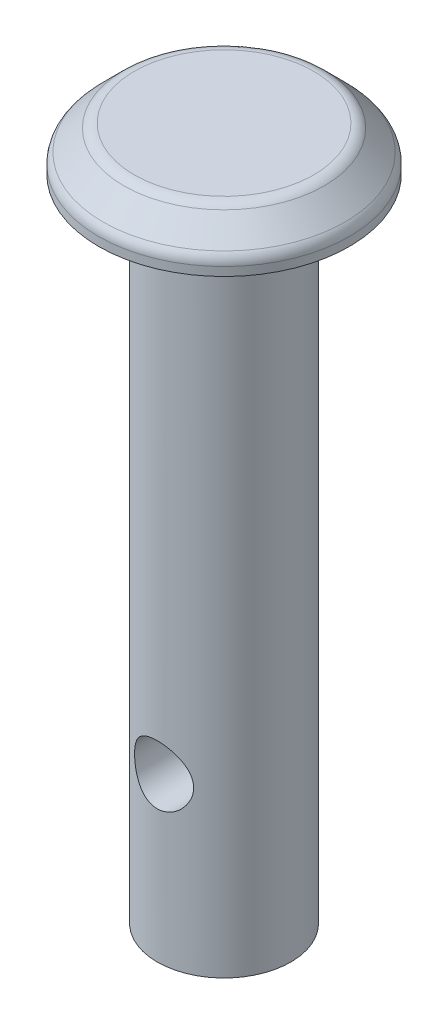
SolidWorks part; units mm, degrees
ref_plane "Front Plane" through (0, 0, 0) normal (0, 0, 1) x (1, 0, 0)
ref_plane "Top Plane" through (0, 0, 0) normal (0, 1, 0) x (1, 0, 0)
ref_plane "Right Plane" through (0, 0, 0) normal (1, 0, 0) x (0, 0, -1)
sketch "Sketch1" plane through (0, 0, 0) normal (0, 1, 0) x (1, 0, 0)
  circle A0 centre (0, 0) radius 2.265
  dimension "D1" = 4.53
extrude "Boss-Extrude1" add sketch "Sketch1" along normal blind 22
sketch "Sketch2" plane through (0, 22, 0) normal (0, 1, 0) x (1, 0, 0)
  circle A0 centre (0, 0) radius 4.25
  dimension "D1" = 8.5
extrude "Boss-Extrude2" add sketch "Sketch2" along normal blind 1.5
chamfer "Chamfer1" distance 1 angle 45 1 edges at (0, 23.5, 4.25)
fillet "Fillet1" radius 0.5 2 edges at (0, 22.5, 4.25) (0, 23.5, 3.25)
sketch "Sketch3" plane through (0, 0, 0) normal (0, 0, 1) x (1, 0, 0)
  line L0 (-2.265, 0) -> (2.265, 0) construction
  circle A0 centre (0, 5.5) radius 1
  point P2 (0, 0)
  dimension "D2" = 2
  dimension "D1" = 5.5
extrude "Cut-Extrude1" cut sketch "Sketch3" against normal through all both and the other way through all
